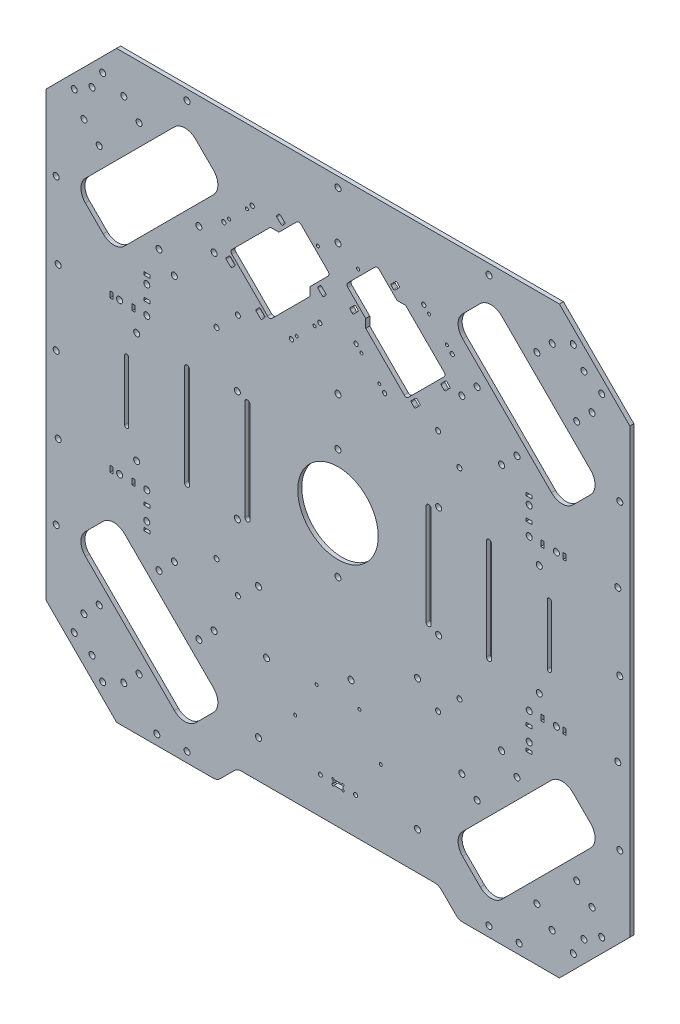
SolidWorks part; units mm, degrees
material "6061 合金"
ref_plane "前视基准面" through (0, 0, 0) normal (0, 0, 1) x (1, 0, 0)
ref_plane "上视基准面" through (0, 0, 0) normal (0, 1, 0) x (1, 0, 0)
ref_plane "右视基准面" through (0, 0, 0) normal (1, 0, 0) x (0, 0, -1)
sketch "草图1" plane through (0, 0, 0) normal (0, 0, 1) x (1, 0, 0)
  line L1 (-290, 290) -> (290, 290)
  line L2 (-290, 290) -> (-290, -290)
  line L3 (-290, -290) -> (290, -290)
  line L4 (290, 290) -> (290, -290)
  line L5 (-290, 290) -> (290, -290) construction
  line L6 (-290, -290) -> (290, 290) construction
  point P0 (0, 0)
  dimension "D1" = 580
  dimension "D2" = 580
extrude "凸台-拉伸1" add sketch "草图1" along normal blind 4
chamfer "倒角1" distance 70 angle 45 4 edges at (-290, 290, 2) (290, 290, 2) (290, -290, 2) (-290, -290, 2)
sketch "草图2" plane through (0, 0, 4) normal (0, 0, 1) x (1, 0, 0)
  circle A0 centre (0, 0) radius 40
  dimension "D1" = 80
extrude "切除-拉伸1" cut sketch "草图2" against normal through all
sketch "草图3" plane through (0, 0, 4) normal (0, 0, 1) x (1, 0, 0)
  line L0 (-256.1836, 0) -> (290.6437, 0) construction
  line L1 (0, 0) -> (-206.4276, -206.4276) construction
  line L3 (-162.6346, -123.0366) -> (-177.8374, -138.2394) construction
  circle A0 centre (-162.6346, -123.0366) radius 3
  circle A1 centre (-177.8374, -138.2394) radius 3
  circle A2 centre (-138.2394, -177.8374) radius 3
  circle A3 centre (-123.0366, -162.6346) radius 3
  circle A4 centre (-123.0366, 162.6346) radius 3
  circle A5 centre (-138.2394, 177.8374) radius 3
  circle A6 centre (-162.6346, 123.0366) radius 3
  circle A7 centre (-177.8374, 138.2394) radius 3
  circle A8 centre (162.6346, 123.0366) radius 3
  circle A9 centre (177.8374, 138.2394) radius 3
  circle A10 centre (123.0366, 162.6346) radius 3
  circle A11 centre (138.2394, 177.8374) radius 3
  circle A12 centre (123.0366, -162.6346) radius 3
  circle A13 centre (138.2394, -177.8374) radius 3
  circle A14 centre (162.6346, -123.0366) radius 3
  circle A15 centre (177.8374, -138.2394) radius 3
  point P42 (0, 0)
  dimension "D1" = 6
  dimension "D2" = 6
  dimension "D4" = 45
  dimension "D3" = 6
  dimension "D5" = 4
extrude "切除-拉伸3" cut sketch "草图3" against normal through all
sketch "草图8" plane through (0, 0, 0) normal (0, 0, -1) x (-1, 0, 0)
  line L0 (-432.8863, 0) -> (443.6169, 0) construction
  line L1 (0, 328.7711) -> (0, -317.5393) construction
  circle A2 centre (-190, 75) radius 3
  circle A3 centre (-190, -75) radius 3
  circle A6 centre (190, 75) radius 3
  circle A11 centre (190, -75) radius 3
  dimension "D1" = 190
  dimension "D2" = 150
  dimension "D9" = 6
extrude "切除-拉伸6" cut sketch "草图8" against normal through all
sketch "草图12" plane through (0, 0, 4) normal (0, 0, 1) x (1, 0, 0)
  line L0 (190, 75) -> (190, 104.688) construction
  line L1 (226.5, 72) -> (223.5, 78) construction
  line L2 (223.5, 72) -> (226.5, 78) construction
  line L3 (204.5, 72) -> (201.5, 78) construction
  line L4 (201.5, 72) -> (204.5, 78) construction
  line L5 (223.5, 78) -> (226.5, 78)
  line L6 (226.5, 72) -> (226.5, 78)
  line L7 (187, 86.5) -> (193, 86.5)
  line L8 (187, 86.5) -> (187, 89.5)
  line L9 (187, 89.5) -> (193, 89.5)
  line L10 (193, 86.5) -> (193, 89.5)
  line L11 (187, 86.5) -> (193, 89.5) construction
  line L12 (187, 89.5) -> (193, 86.5) construction
  line L13 (190, 75) -> (222.9919, 107.9919) construction
  line L14 (223.5, 72) -> (226.5, 72)
  line L15 (223.5, 72) -> (223.5, 78)
  line L16 (201.5, 78) -> (204.5, 78)
  line L17 (204.5, 72) -> (204.5, 78)
  line L18 (201.5, 72) -> (204.5, 72)
  line L19 (190, 75) -> (228.7933, 75) construction
  line L20 (201.5, 72) -> (201.5, 78)
  line L21 (187, 108.5) -> (193, 108.5)
  line L22 (187, 108.5) -> (187, 111.5)
  line L23 (187, 111.5) -> (193, 111.5)
  line L24 (193, 108.5) -> (193, 111.5)
  line L25 (187, 108.5) -> (193, 111.5) construction
  line L26 (187, 111.5) -> (193, 108.5) construction
  line L27 (98.4572, 0) -> (401.3227, 0) construction
  line L28 (201.5, -72) -> (204.5, -78) construction
  line L29 (204.5, -72) -> (201.5, -78) construction
  line L30 (223.5, -72) -> (226.5, -78) construction
  line L31 (226.5, -72) -> (223.5, -78) construction
  line L32 (201.5, -72) -> (201.5, -78)
  line L33 (201.5, -72) -> (204.5, -72)
  line L34 (204.5, -72) -> (204.5, -78)
  line L35 (201.5, -78) -> (204.5, -78)
  line L36 (223.5, -72) -> (223.5, -78)
  line L37 (223.5, -72) -> (226.5, -72)
  line L38 (226.5, -72) -> (226.5, -78)
  line L39 (223.5, -78) -> (226.5, -78)
  line L40 (187, -111.5) -> (193, -108.5) construction
  line L41 (187, -108.5) -> (193, -111.5) construction
  line L42 (187, -89.5) -> (193, -86.5) construction
  line L43 (187, -86.5) -> (193, -89.5) construction
  line L44 (193, -108.5) -> (193, -111.5)
  line L45 (187, -111.5) -> (193, -111.5)
  line L46 (187, -108.5) -> (187, -111.5)
  line L47 (187, -108.5) -> (193, -108.5)
  line L48 (193, -86.5) -> (193, -89.5)
  line L49 (187, -89.5) -> (193, -89.5)
  line L50 (187, -86.5) -> (187, -89.5)
  line L51 (187, -86.5) -> (193, -86.5)
  line L52 (0, 241.3028) -> (0, -339.5284) construction
  line L53 (-187, -86.5) -> (-193, -89.5) construction
  line L54 (-187, -89.5) -> (-193, -86.5) construction
  line L55 (-187, -108.5) -> (-193, -111.5) construction
  line L56 (-187, -111.5) -> (-193, -108.5) construction
  line L57 (-226.5, -72) -> (-223.5, -78) construction
  line L58 (-223.5, -72) -> (-226.5, -78) construction
  line L59 (-204.5, -72) -> (-201.5, -78) construction
  line L60 (-201.5, -72) -> (-204.5, -78) construction
  line L61 (-187, -86.5) -> (-193, -86.5)
  line L62 (-187, -86.5) -> (-187, -89.5)
  line L63 (-187, -89.5) -> (-193, -89.5)
  line L64 (-193, -86.5) -> (-193, -89.5)
  line L65 (-187, -108.5) -> (-193, -108.5)
  line L66 (-187, -108.5) -> (-187, -111.5)
  line L67 (-187, -111.5) -> (-193, -111.5)
  line L68 (-193, -108.5) -> (-193, -111.5)
  line L69 (-223.5, -78) -> (-226.5, -78)
  line L70 (-226.5, -72) -> (-226.5, -78)
  line L71 (-223.5, -72) -> (-226.5, -72)
  line L72 (-223.5, -72) -> (-223.5, -78)
  line L73 (-201.5, -78) -> (-204.5, -78)
  line L74 (-204.5, -72) -> (-204.5, -78)
  line L75 (-201.5, -72) -> (-204.5, -72)
  line L76 (-201.5, -72) -> (-201.5, -78)
  line L77 (-187, 111.5) -> (-193, 108.5) construction
  line L78 (-187, 108.5) -> (-193, 111.5) construction
  line L79 (-187, 89.5) -> (-193, 86.5) construction
  line L80 (-187, 86.5) -> (-193, 89.5) construction
  line L81 (-201.5, 72) -> (-204.5, 78) construction
  line L82 (-204.5, 72) -> (-201.5, 78) construction
  line L83 (-223.5, 72) -> (-226.5, 78) construction
  line L84 (-226.5, 72) -> (-223.5, 78) construction
  line L85 (-193, 108.5) -> (-193, 111.5)
  line L86 (-187, 111.5) -> (-193, 111.5)
  line L87 (-187, 108.5) -> (-187, 111.5)
  line L88 (-187, 108.5) -> (-193, 108.5)
  line L89 (-201.5, 72) -> (-201.5, 78)
  line L90 (-201.5, 72) -> (-204.5, 72)
  line L91 (-204.5, 72) -> (-204.5, 78)
  line L92 (-201.5, 78) -> (-204.5, 78)
  line L93 (-223.5, 72) -> (-223.5, 78)
  line L94 (-223.5, 72) -> (-226.5, 72)
  line L95 (-193, 86.5) -> (-193, 89.5)
  line L96 (-187, 89.5) -> (-193, 89.5)
  line L97 (-187, 86.5) -> (-187, 89.5)
  line L98 (-187, 86.5) -> (-193, 86.5)
  line L99 (-226.5, 72) -> (-226.5, 78)
  line L100 (-223.5, 78) -> (-226.5, 78)
  circle A0 centre (190, 102) radius 3
  circle A1 centre (217, 75) radius 3
  circle A2 centre (217, -75) radius 3
  circle A3 centre (190, -102) radius 3
  circle A4 centre (-190, -102) radius 3
  circle A5 centre (-217, -75) radius 3
  circle A6 centre (-217, 75) radius 3
  circle A7 centre (-190, 102) radius 3
  point P6 (190, 88)
  point P20 (190, 110)
  point P27 (225, 75)
  point P28 (203, 75)
  point P43 (203, -75)
  point P44 (225, -75)
  point P56 (190, -110)
  point P57 (190, -88)
  point P80 (-190, -88)
  point P81 (-190, -110)
  point P82 (-225, -75)
  point P83 (-203, -75)
  point P104 (-203, 75)
  point P105 (-225, 75)
  point P106 (-190, 110)
  point P107 (-190, 88)
  dimension "D6" = 6
  dimension "D2" = 45
  dimension "D3" = 11.5
  dimension "D4" = 3
  dimension "D5" = 6
  dimension "D7" = 6
  dimension "D8" = 3
  dimension "D9" = 12.5
  dimension "D10" = 6.5
extrude "切除-拉伸7" cut sketch "草图12" against normal through all
sketch "草图13" plane through (0, 0, 4) normal (0, 0, 1) x (1, 0, 0)
  line L0 (-222.7386, -113.1371) -> (-261.6295, -152.028)
  line L1 (-261.6295, -152.028) -> (-152.028, -261.6295)
  line L2 (-152.028, -261.6295) -> (-113.1371, -222.7386)
  line L3 (-113.1371, -222.7386) -> (-222.7386, -113.1371)
  line L4 (0, 0) -> (-260.9539, -260.9539) construction
  line L5 (-220, -290) -> (220, -290) construction
  line L6 (-206.7922, -167.9744) -> (-258.1111, -116.6555) construction
  line L7 (0, 0) -> (-76.238, 76.238) construction
  line L11 (-113.1371, 222.7386) -> (-152.028, 261.6295)
  line L12 (-152.028, 261.6295) -> (-261.6295, 152.028)
  line L13 (-261.6295, 152.028) -> (-222.7386, 113.1371)
  line L14 (-222.7386, 113.1371) -> (-113.1371, 222.7386)
  line L15 (222.7386, 113.1371) -> (261.6295, 152.028)
  line L16 (261.6295, 152.028) -> (152.028, 261.6295)
  line L17 (152.028, 261.6295) -> (113.1371, 222.7386)
  line L18 (113.1371, 222.7386) -> (222.7386, 113.1371)
  line L19 (113.1371, -222.7386) -> (152.028, -261.6295)
  line L20 (152.028, -261.6295) -> (261.6295, -152.028)
  line L21 (261.6295, -152.028) -> (222.7386, -113.1371)
  line L22 (222.7386, -113.1371) -> (113.1371, -222.7386)
  point P11 (-232.4516, -142.315)
  point P29 (0, 0)
  dimension "D1" = 45
  dimension "D2" = 55
  dimension "D3" = 155
  dimension "D4" = 4
  dimension "D5" = 265
extrude "切除-拉伸8" cut sketch "草图13" against normal through all
fillet "圆角1" radius 15 16 edges at (-261.6295, 152.028, 2) (-113.1371, 222.7386, 2) (-222.7386, 113.1371, 2) (-152.028, 261.6295, 2) (261.6295, -152.028, 2) (152.028, -261.6295, 2) (222.7386, -113.1371, 2) (113.1371, -222.7386, 2) (152.028, 261.6295, 2) (261.6295, 152.028, 2) (222.7386, 113.1371, 2) (113.1371, 222.7386, 2) (-261.6295, -152.028, 2) (-222.7386, -113.1371, 2) (-113.1371, -222.7386, 2) (-152.028, -261.6295, 2)
sketch "草图14" plane through (0, 0, 0) normal (0, 0, -1) x (-1, 0, 0)
  circle A0 centre (120.7031, -99.4899) radius 2.5
  circle A1 centre (99.4899, -120.7031) radius 2.5
  circle A2 centre (-99.4899, -120.7031) radius 2.5
  circle A3 centre (-120.7031, -99.4899) radius 2.5
  circle A4 centre (-120.7031, 99.4899) radius 2.5
  circle A5 centre (-99.4899, 120.7031) radius 2.5
  circle A6 centre (99.4899, 120.7031) radius 2.5
  circle A7 centre (120.7031, 99.4899) radius 2.5
  point P21 (0, 0)
  dimension "D1" = 5
  dimension "D2" = 5
  dimension "D3" = 4
extrude "切除-拉伸9" cut sketch "草图14" against normal through all
sketch "草图15" plane through (0, 0, 4) normal (0, 0, 1) x (1, 0, 0)
  line L0 (0, 0) -> (-426.7566, 0) construction
  line L1 (-293.2075, -293.2075) -> (0, 0) construction
  line L2 (-252.4371, -212.8391) -> (-237.2343, -197.6363) construction
  line L3 (-251.0229, -162.6346) -> (-162.6346, -251.0229) construction
  circle A0 centre (-252.4371, -212.8391) radius 3
  circle A1 centre (-237.2343, -197.6363) radius 3
  circle A2 centre (-212.8391, -252.4371) radius 3
  circle A3 centre (-197.6363, -237.2343) radius 3
  circle A4 centre (-212.8391, 252.4371) radius 3
  circle A5 centre (-197.6363, 237.2343) radius 3
  circle A6 centre (-252.4371, 212.8391) radius 3
  circle A7 centre (-237.2343, 197.6363) radius 3
  circle A8 centre (252.4371, 212.8391) radius 3
  circle A9 centre (237.2343, 197.6363) radius 3
  circle A10 centre (212.8391, 252.4371) radius 3
  circle A11 centre (197.6363, 237.2343) radius 3
  circle A12 centre (212.8391, -252.4371) radius 3
  circle A13 centre (197.6363, -237.2343) radius 3
  circle A14 centre (252.4371, -212.8391) radius 3
  circle A15 centre (237.2343, -197.6363) radius 3
  point P40 (0, 0)
  dimension "D2" = 6
  dimension "D3" = 6
  dimension "D5" = 56
  dimension "D1" = 45
  dimension "D4" = 21.5
  dimension "D6" = 15
  dimension "D7" = 4
extrude "切除-拉伸10" cut sketch "草图15" against normal through all
sketch "草图16" plane through (0, 0, 4) normal (0, 0, 1) x (1, 0, 0)
  line L0 (0, 336.3235) -> (0, 0) construction
  line L1 (0, 240) -> (65.7609, 174.2391) construction
  line L2 (103.5911, 175.2997) -> (27.9307, 173.1784) construction
  line L3 (64.7003, 136.4089) -> (66.8216, 212.0693) construction
  line L4 (64.7003, 136.4089) -> (27.9307, 173.1784) construction
  line L5 (27.9307, 173.1784) -> (66.8216, 212.0693) construction
  line L6 (66.8216, 212.0693) -> (103.5911, 175.2997) construction
  line L7 (103.5911, 175.2997) -> (64.7003, 136.4089) construction
  line L10 (85.2064, 193.6845) -> (102.1769, 210.6551) construction
  line L11 (46.3155, 154.7936) -> (29.3449, 137.8231) construction
  line L12 (90.5097, 216.6655) -> (108.1873, 198.9878) construction
  circle A0 centre (85.2064, 221.9688) radius 2.1
  circle A1 centre (90.5097, 216.6655) radius 1.5
  circle A2 centre (113.4906, 193.6845) radius 2.1
  circle A3 centre (108.1873, 198.9878) radius 1.5
  circle A4 centre (41.0122, 131.8127) radius 1.5
  circle A5 centre (46.3155, 126.5094) radius 2.1
  circle A6 centre (18.0312, 154.7936) radius 2.1
  circle A7 centre (23.3345, 149.4903) radius 1.5
  circle A8 centre (-46.3155, 126.5094) radius 2.1
  circle A9 centre (-41.0122, 131.8127) radius 1.5
  circle A10 centre (-23.3345, 149.4903) radius 1.5
  circle A11 centre (-18.0312, 154.7936) radius 2.1
  circle A12 centre (-108.1873, 198.9878) radius 1.5
  circle A13 centre (-113.4906, 193.6845) radius 2.1
  circle A14 centre (-85.2064, 221.9688) radius 2.1
  circle A15 centre (-90.5097, 216.6655) radius 1.5
  dimension "D7" = 4.2
  dimension "D8" = 3
  dimension "D9" = 4.2
  dimension "D10" = 240
  dimension "D11" = 40
  dimension "D12" = 25
  dimension "D2" = 55
  dimension "D3" = 52
  dimension "D4" = 93
  dimension "D5" = 24
  dimension "D6" = 4
  dimension "D13" = 45
extrude "切除-拉伸11" cut sketch "草图16" against normal through all
sketch "草图17" plane through (0, 0, 4) normal (0, 0, 1) x (1, 0, 0)
  line L0 (7.7782, 201.1091) -> (38.8909, 232.2218)
  line L1 (0, 240) -> (65.7609, 174.2391) construction
  line L2 (38.8909, 232.2218) -> (62.9325, 208.1802)
  line L4 (62.9325, 208.1802) -> (67.1751, 212.4228)
  line L5 (67.1751, 212.4228) -> (107.4802, 172.1177)
  line L6 (107.4802, 172.1177) -> (67.8823, 132.5198)
  line L8 (103.5911, 175.2997) -> (64.7003, 136.4089) construction
  line L9 (0, 240) -> (47.5, 192.5) construction
  line L10 (27.5772, 172.8249) -> (67.8823, 132.5198)
  line L11 (31.8198, 177.0675) -> (27.5772, 172.8249)
  line L12 (7.7782, 201.1091) -> (31.8198, 177.0675)
  line L13 (27.9307, 173.1784) -> (66.8216, 212.0693) construction
  line L14 (0, 0) -> (0, 362.1527) construction
  line L15 (-7.7782, 201.1091) -> (-31.8198, 177.0675)
  line L16 (-31.8198, 177.0675) -> (-27.5772, 172.8249)
  line L17 (-27.5772, 172.8249) -> (-67.8823, 132.5198)
  line L18 (-107.4802, 172.1177) -> (-67.8823, 132.5198)
  line L19 (-67.1751, 212.4228) -> (-107.4802, 172.1177)
  line L20 (-62.9325, 208.1802) -> (-67.1751, 212.4228)
  line L21 (-38.8909, 232.2218) -> (-62.9325, 208.1802)
  line L22 (-7.7782, 201.1091) -> (-38.8909, 232.2218)
  point P17 (87.6812, 152.3188)
  point P20 (23.3345, 216.6655)
  point P24 (-23.3345, 216.6655)
  point P25 (-87.6812, 152.3188)
  dimension "D1" = 22
  dimension "D2" = 28
  dimension "D3" = 33
  dimension "D4" = 5
extrude "切除-拉伸12" cut sketch "草图17" against normal through all
fillet "圆角2" radius 3 8 edges at (67.8823, 132.5198, 2) (7.7782, 201.1091, 2) (38.8909, 232.2218, 2) (107.4802, 172.1177, 2) (-107.4802, 172.1177, 2) (-38.8909, 232.2218, 2) (-7.7782, 201.1091, 2) (-67.8823, 132.5198, 2)
chamfer "倒角2" distance 6 angle 45 4 edges at (62.9325, 208.1802, 2) (31.8198, 177.0675, 2) (-31.8198, 177.0675, 2) (-62.9325, 208.1802, 2)
fillet "圆角3" [suppressed] radius 30
sketch "草图18" plane through (0, 0, 4) normal (0, 0, 1) x (1, 0, 0)
  line L0 (0, 235.9028) -> (0, -79.4004) construction
  circle A0 centre (-20, 220) radius 1.5
  circle A1 centre (20, 220) radius 1.5
  dimension "D1" = 3
  dimension "D2" = 40
  dimension "D3" = 220
extrude "切除-拉伸13" cut sketch "草图18" against normal through all
sketch "草图19" plane through (0, 0, 4) normal (0, 0, 1) x (1, 0, 0)
  line L0 (52.3259, 223.0294) -> (55.8614, 219.4939)
  line L1 (55.8614, 219.4939) -> (61.5183, 225.1508)
  line L2 (61.5183, 225.1508) -> (57.9828, 228.6863)
  line L3 (57.9828, 228.6863) -> (52.3259, 223.0294)
  line L4 (58.6899, 212.4228) -> (41.0122, 230.1005) construction
  line L5 (36.7696, 230.1005) -> (9.8995, 203.2304) construction
  line L6 (-23.3345, 216.6655) -> (-96.6763, 143.3237) construction
  line L7 (23.3345, 216.6655) -> (96.6763, 143.3237) construction
  line L8 (107.4802, 167.8751) -> (101.8234, 162.2183)
  line L9 (101.8234, 162.2183) -> (106.066, 157.9756)
  line L10 (106.066, 157.9756) -> (111.7229, 163.6325)
  line L11 (111.7229, 163.6325) -> (107.4802, 167.8751)
  line L12 (70.0036, 134.6411) -> (105.3589, 169.9964) construction
  line L13 (105.3589, 174.2391) -> (67.1751, 212.4228) construction
  line L14 (76.3675, 128.2771) -> (72.1249, 132.5198)
  line L15 (82.0244, 133.934) -> (76.3675, 128.2771)
  line L16 (77.7817, 138.1766) -> (82.0244, 133.934)
  line L17 (72.1249, 132.5198) -> (77.7817, 138.1766)
  line L18 (11.3137, 182.0172) -> (16.9706, 187.6741)
  line L19 (14.8492, 178.4817) -> (11.3137, 182.0172)
  line L20 (20.5061, 184.1386) -> (14.8492, 178.4817)
  line L21 (16.9706, 187.6741) -> (20.5061, 184.1386)
  line L22 (0, 349.7726) -> (0, -22.9654) construction
  line L23 (-16.9706, 187.6741) -> (-20.5061, 184.1386)
  line L24 (-20.5061, 184.1386) -> (-14.8492, 178.4817)
  line L25 (-14.8492, 178.4817) -> (-11.3137, 182.0172)
  line L26 (-11.3137, 182.0172) -> (-16.9706, 187.6741)
  line L27 (-72.1249, 132.5198) -> (-77.7817, 138.1766)
  line L28 (-77.7817, 138.1766) -> (-82.0244, 133.934)
  line L29 (-82.0244, 133.934) -> (-76.3675, 128.2771)
  line L30 (-76.3675, 128.2771) -> (-72.1249, 132.5198)
  line L31 (-111.7229, 163.6325) -> (-107.4802, 167.8751)
  line L32 (-106.066, 157.9756) -> (-111.7229, 163.6325)
  line L33 (-101.8234, 162.2183) -> (-106.066, 157.9756)
  line L34 (-107.4802, 167.8751) -> (-101.8234, 162.2183)
  line L35 (-57.9828, 228.6863) -> (-52.3259, 223.0294)
  line L36 (-61.5183, 225.1508) -> (-57.9828, 228.6863)
  line L37 (-55.8614, 219.4939) -> (-61.5183, 225.1508)
  line L38 (-52.3259, 223.0294) -> (-55.8614, 219.4939)
  dimension "D1" = 5
  dimension "D2" = 8
  dimension "D3" = 3
  dimension "D4" = 16
  dimension "D5" = 3
  dimension "D6" = 8
  dimension "D7" = 6
  dimension "D8" = 3
extrude "切除-拉伸14" cut sketch "草图19" against normal through all
fillet "圆角4" radius 1 32 edges at (-77.7817, 138.1766, 2) (-72.1249, 132.5198, 2) (-76.3675, 128.2771, 2) (-82.0244, 133.934, 2) (-107.4802, 167.8751, 2) (-101.8234, 162.2183, 2) (-106.066, 157.9756, 2) (-111.7229, 163.6325, 2) (-52.3259, 223.0294, 2) (-55.8614, 219.4939, 2) (-57.9828, 228.6863, 2) (-61.5183, 225.1508, 2) (-14.8492, 178.4817, 2) (-16.9706, 187.6741, 2) (-11.3137, 182.0172, 2) (-20.5061, 184.1386, 2) (16.9706, 187.6741, 2) (20.5061, 184.1386, 2) (14.8492, 178.4817, 2) (11.3137, 182.0172, 2) (77.7817, 138.1766, 2) (82.0244, 133.934, 2) (76.3675, 128.2771, 2) (72.1249, 132.5198, 2) (106.066, 157.9756, 2) (107.4802, 167.8751, 2) (111.7229, 163.6325, 2) (101.8234, 162.2183, 2) (61.5183, 225.1508, 2) (55.8614, 219.4939, 2) (57.9828, 228.6863, 2) (52.3259, 223.0294, 2)
sketch "草图20" plane through (0, 0, 4) normal (0, 0, 1) x (1, 0, 0)
  line L0 (0, -67.8843) -> (0, -369.1662) construction
  line L1 (-120, -290) -> (-100, -270)
  line L2 (-220, -290) -> (220, -290) construction
  line L3 (120, -290) -> (100, -270)
  line L4 (-100, -270) -> (100, -270)
  line L5 (-120, -290) -> (120, -290)
  dimension "D1" = 45
  dimension "D2" = 240
  dimension "D3" = 20
extrude "切除-拉伸15" cut sketch "草图20" against normal through all
fillet "圆角5" radius 10 4 edges at (100, -270, 2) (120, -290, 2) (-100, -270, 2) (-120, -290, 2)
sketch "草图21" plane through (0, 0, 4) normal (0, 0, 1) x (1, 0, 0)
  line L0 (0, 0) -> (0, -195) construction
  line L1 (-21.25, -158.1939) -> (0, -195) construction
  circle A0 centre (0, -195) radius 42.5 construction
  circle A1 centre (-21.25, -158.1939) radius 1.5
  circle A2 centre (21.25, -158.1939) radius 1.5
  circle A3 centre (42.5, -195) radius 1.5
  circle A6 centre (-42.5, -195) radius 1.5
  circle A7 centre (-21.25, -231.8061) radius 1.5 [skipped]
  circle A8 centre (21.25, -231.8061) radius 1.5 [skipped]
  circle A9 centre (-17.5, -233.7298) radius 2
  circle A10 centre (17.5, -233.7298) radius 2
  point P18 (0, -195)
  dimension "D1" = 85
  dimension "D3" = 3
  dimension "D6" = 4
  dimension "D8" = 35
  dimension "D2" = 195
  dimension "D4" = 30
  dimension "D5" = 6
extrude "切除-拉伸16" cut sketch "草图21" against normal through all
sketch "草图22" plane through (0, 0, 4) normal (0, 0, 1) x (1, 0, 0)
  line L0 (13, -12.0575) -> (13, -305.8165) construction
  line L1 (-71, -48.2048) -> (-71, -331.3779) construction
  line L4 (3, -127) -> (23, -127) construction
  line L5 (3, -127) -> (3, -147) construction
  line L6 (3, -147) -> (23, -147) construction
  line L7 (23, -127) -> (23, -147) construction
  line L8 (3, -127) -> (23, -147) construction
  line L9 (3, -147) -> (23, -127) construction
  line L10 (-81, -150) -> (-61, -150) construction
  line L11 (-81, -150) -> (-81, -170) construction
  line L12 (-81, -170) -> (-61, -170) construction
  line L13 (-61, -150) -> (-61, -170) construction
  line L14 (-81, -150) -> (-61, -170) construction
  line L15 (-81, -170) -> (-61, -150) construction
  circle A0 centre (13, -137) radius 3
  circle A1 centre (-71, -160) radius 3
  circle A22 centre (0, -195) radius 46 construction
  dimension "D1" = 6
  dimension "D2" = 6
  dimension "D8" = 92
  dimension "D3" = 13
  dimension "D4" = 71
  dimension "D5" = 2
  dimension "D6" = 20
  dimension "D7" = 20
  dimension "D9" = 160
extrude "切除-拉伸17" cut sketch "草图22" against normal through all
sketch "草图23" plane through (0, 0, 4) normal (0, 0, 1) x (1, 0, 0)
  line L0 (-17.5, -233.7298) -> (17.5, -233.7298) construction
  line L2 (-5, -231.2298) -> (5, -231.2298)
  line L3 (-5, -231.2298) -> (-5, -236.2298)
  line L4 (-5, -236.2298) -> (5, -236.2298)
  line L5 (5, -231.2298) -> (5, -236.2298)
  line L6 (-5, -231.2298) -> (5, -236.2298) construction
  line L7 (-5, -236.2298) -> (5, -231.2298) construction
  point P4 (0, -233.7298)
  dimension "D1" = 5
  dimension "D2" = 10
extrude "切除-拉伸18" cut sketch "草图23" against normal through all
sketch "草图24" plane through (0, 0, 4) normal (0, 0, 1) x (1, 0, 0)
  circle A0 centre (-5, -231.2298) radius 1
  circle A1 centre (5, -231.2298) radius 1
  circle A2 centre (-5, -236.2298) radius 1
  circle A3 centre (5, -236.2298) radius 1
  dimension "D1" = 2
  dimension "D2" = 2
  dimension "D3" = 2
  dimension "D4" = 2
extrude "切除-拉伸19" cut sketch "草图24" against normal through all
sketch "草图25" plane through (0, 0, 4) normal (0, 0, 1) x (1, 0, 0)
  line L0 (190, 75) -> (365.1287, 75) construction
  line L1 (290, -220) -> (290, 220) construction
  line L2 (251.0882, 0) -> (360.1957, 0) construction
  line L3 (0, 322.7651) -> (0, -287.6418) construction
  circle A0 centre (278, 75) radius 3
  circle A1 centre (278, -75) radius 3
  circle A2 centre (-278, -75) radius 3
  circle A3 centre (-278, 75) radius 3
  dimension "D1" = 6
  dimension "D2" = 12
extrude "切除-拉伸20" cut sketch "草图25" against normal through all
sketch "草图26" plane through (0, 0, 4) normal (0, 0, 1) x (1, 0, 0)
  line L0 (-212.8391, 252.4371) -> (-252.4371, 212.8391) construction
  line L1 (-244.3934, 244.3934) -> (-232.6381, 232.6381) construction
  line L2 (-220, 290) -> (-290, 220) construction
  circle A0 centre (-244.3934, 244.3934) radius 3
  circle A1 centre (244.3934, 244.3934) radius 3
  circle A2 centre (244.3934, -244.3934) radius 3
  circle A3 centre (-244.3934, -244.3934) radius 3
  point P15 (0, 0)
  dimension "D1" = 6
  dimension "D2" = 4
  dimension "D3" = 15
extrude "切除-拉伸21" cut sketch "草图26" against normal through all
sketch "草图27" plane through (0, 0, 4) normal (0, 0, 1) x (1, 0, 0)
  line L0 (0, 342.6644) -> (0, -34.9873) construction
  line L1 (220, 290) -> (-220, 290) construction
  line L2 (-150, 280) -> (0, 280) construction
  circle A0 centre (-150, 280) radius 3
  circle A1 centre (150, 280) radius 3
  circle A2 centre (0, 280) radius 3
  circle A3 centre (280, 150) radius 3
  circle A4 centre (280, 0) radius 3
  circle A5 centre (280, -150) radius 3
  circle A6 centre (150, -280) radius 3
  circle A7 centre (0, -280) radius 3
  circle A8 centre (-150, -280) radius 3
  circle A9 centre (-280, -150) radius 3
  circle A10 centre (-280, 0) radius 3
  circle A11 centre (-280, 150) radius 3
  point P32 (0, 0)
  dimension "D1" = 6
  dimension "D2" = 300
  dimension "D3" = 10
  dimension "D4" = 6
  dimension "D5" = 4
extrude "切除-拉伸22" cut sketch "草图27" against normal through all
sketch "草图29" plane through (0, 0, 4) normal (0, 0, 1) x (1, 0, 0)
  line L0 (0, 0) -> (0, -436.3201) construction
  line L1 (124.1421, -290) -> (220, -290) construction
  line L2 (170, -270) -> (190, -270) construction
  line L3 (170, -270) -> (170, -290) construction
  line L4 (170, -290) -> (190, -290) construction
  line L5 (190, -270) -> (190, -290) construction
  line L6 (170, -270) -> (190, -290) construction
  line L7 (170, -290) -> (190, -270) construction
  circle A0 centre (180, -280) radius 3
  circle A1 centre (180, -280) radius 14.1421 construction
  circle A2 centre (-180, -280) radius 3
  dimension "D1" = 6
  dimension "D3" = 10
  dimension "D2" = 20
  dimension "D4" = 180
extrude "切除-拉伸24" cut sketch "草图29" against normal through all
sketch "草图28" plane through (0, 0, 4) normal (0, 0, 1) x (1, 0, 0)
  line L0 (90, -50) -> (90, 50) construction
  line L1 (87.5, -50) -> (87.5, 50)
  line L2 (92.5, -50) -> (92.5, 50)
  line L3 (150, -50) -> (150, 50) construction
  line L4 (147.5, -50) -> (147.5, 50)
  line L5 (152.5, -50) -> (152.5, 50)
  line L6 (210, 30) -> (210, -30) construction
  line L7 (212, 30) -> (212, -30)
  line L8 (208, 30) -> (208, -30)
  line L9 (0, 0) -> (323.8087, 0) construction
  line L10 (0, 238.3629) -> (0, -293.4659) construction
  line L11 (-90, -50) -> (-90, 50) construction
  line L12 (-87.5, -50) -> (-87.5, 50)
  line L13 (-92.5, -50) -> (-92.5, 50)
  line L14 (-150, -50) -> (-150, 50) construction
  line L15 (-147.5, -50) -> (-147.5, 50)
  line L16 (-152.5, -50) -> (-152.5, 50)
  line L17 (-210, 30) -> (-210, -30) construction
  line L18 (-212, 30) -> (-212, -30)
  line L19 (-208, 30) -> (-208, -30)
  arc A0 (87.5, -50) -> (92.5, -50) centre (90, -50) ccw
  arc A1 (92.5, 50) -> (87.5, 50) centre (90, 50) ccw
  arc A2 (147.5, -50) -> (152.5, -50) centre (150, -50) ccw
  arc A3 (152.5, 50) -> (147.5, 50) centre (150, 50) ccw
  arc A4 (212, 30) -> (208, 30) centre (210, 30) ccw
  arc A5 (208, -30) -> (212, -30) centre (210, -30) ccw
  arc A6 (-87.5, -50) -> (-92.5, -50) centre (-90, -50) cw
  arc A7 (-92.5, 50) -> (-87.5, 50) centre (-90, 50) cw
  arc A8 (-147.5, -50) -> (-152.5, -50) centre (-150, -50) cw
  arc A9 (-152.5, 50) -> (-147.5, 50) centre (-150, 50) cw
  arc A10 (-212, 30) -> (-208, 30) centre (-210, 30) cw
  arc A11 (-208, -30) -> (-212, -30) centre (-210, -30) cw
  point P2 (90, 0)
  point P8 (150, 0)
  point P15 (210, 0)
  point P26 (-90, 0)
  point P35 (-150, 0)
  point P42 (-210, 0)
  dimension "D1" = 5
  dimension "D2" = 5
  dimension "D3" = 4
  dimension "D4" = 60
  dimension "D5" = 100
  dimension "D6" = 100
  dimension "D7" = 90
  dimension "D8" = 150
  dimension "D9" = 210
extrude "切除-拉伸23" cut sketch "草图28" against normal through all
sketch "草图31" plane through (0, 0, 4) normal (0, 0, 1) x (1, 0, 0)
  line L0 (-205.8579, 290) -> (-290, 205.8579) construction
  line L1 (220, 290) -> (-220, 290) construction
  line L2 (-290, 220) -> (-290, -220) construction
  line L3 (-220, 290) -> (-290, 220) construction
  circle A0 centre (-233.7868, 262.0711) radius 3
  circle A1 centre (-262.0711, 233.7868) radius 3
  circle A2 centre (233.7868, 262.0711) radius 3
  circle A3 centre (262.0711, 233.7868) radius 3
  circle A4 centre (262.0711, -233.7868) radius 3
  circle A5 centre (233.7868, -262.0711) radius 3
  circle A6 centre (-233.7868, -262.0711) radius 3
  circle A7 centre (-262.0711, -233.7868) radius 3
  point P12 (-247.9289, 247.9289)
  point P28 (0, 0)
  dimension "D2" = 6
  dimension "D3" = 6
  dimension "D1" = 10
  dimension "D4" = 20
  dimension "D5" = 20
  dimension "D6" = 4
extrude "切除-拉伸25" cut sketch "草图31" against normal blind 10
sketch "草图33" plane through (0, 0, 4) normal (0, 0, 1) x (1, 0, 0)
  line L0 (-290, 0) -> (290, 0) construction
  line L1 (-290, 220) -> (-290, -220) construction
  line L2 (290, -220) -> (290, 220) construction
  line L3 (-290, 55) -> (290, 55) construction
  circle A0 centre (0, 55) radius 3
  circle A1 centre (100, 55) radius 3
  circle A2 centre (200, 55) radius 3
  circle A4 centre (-200, 55) radius 3
  circle A5 centre (-100, 55) radius 3
  circle A6 centre (200, -55) radius 3
  circle A7 centre (-100, -55) radius 3
  circle A8 centre (-200, -55) radius 3
  circle A9 centre (100, -55) radius 3
  circle A10 centre (0, -55) radius 3
  dimension "D2" = 6
  dimension "D3" = 6
  dimension "D4" = 6
  dimension "D5" = 6
  dimension "D6" = 6
  dimension "D9" = 100
  dimension "D1" = 55
  dimension "D7" = 100
  dimension "D8" = 100
  dimension "D10" = 200
extrude "切除-拉伸26" cut sketch "草图33" against normal blind 10
sketch "草图34" plane through (0, 0, 4) normal (0, 0, 1) x (1, 0, 0)
  line L0 (0, 290) -> (0, -270) construction
  line L1 (220, 290) -> (-220, 290) construction
  line L2 (95.8579, -270) -> (-95.8579, -270) construction
  circle A0 centre (0, 232.5) radius 3
  circle A1 centre (0, 102.5) radius 3
  dimension "D1" = 6
  dimension "D2" = 57.5
  dimension "D3" = 6
  dimension "D4" = 130
extrude "切除-拉伸27" cut sketch "草图34" against normal blind 10
sketch "草图35" plane through (0, 0, 4) normal (0, 0, 1) x (1, 0, 0)
  line L0 (0, 0) -> (0, -270) construction
  line L1 (95.8579, -270) -> (-95.8579, -270) construction
  line L2 (-79, -270) -> (-79, -118.7463) construction
  line L3 (-220, -290) -> (-124.1421, -290) construction
  line L4 (79, -270) -> (79, -118.7463) construction
  circle A0 centre (-79, -232.5) radius 3
  circle A1 centre (-79, -102.5) radius 3
  circle A2 centre (79, -102.5) radius 3
  circle A3 centre (79, -232.5) radius 3
  dimension "D2" = 6
  dimension "D3" = 6
  dimension "D1" = 79
  dimension "D4" = 57.5
  dimension "D5" = 130
extrude "切除-拉伸28" cut sketch "草图35" against normal blind 10
